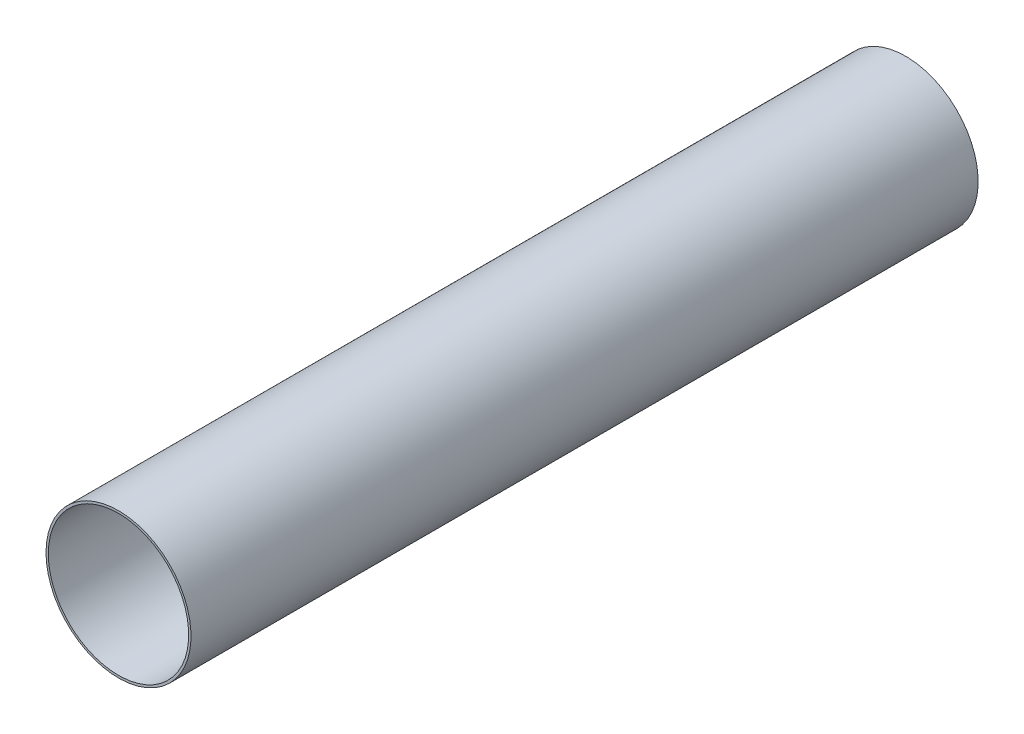
SolidWorks part; units mm, degrees
ref_plane "Front Plane" through (0, 0, 0) normal (0, 0, 1) x (1, 0, 0)
ref_plane "Top Plane" through (0, 0, 0) normal (0, 1, 0) x (1, 0, 0)
ref_plane "Right Plane" through (0, 0, 0) normal (1, 0, 0) x (0, 0, -1)
sketch "Sketch1" plane through (0, 0, 0) normal (0, 0, 1) x (1, 0, 0)
  circle A0 centre (0, 0) radius 28.067
  circle A1 centre (0, 0) radius 27.178
  dimension "D1" = 56.134
  dimension "D2" = 54.356
  dimension "D3" = 0.889
extrude "Boss-Extrude1" add sketch "Sketch1" along normal blind 304.8
